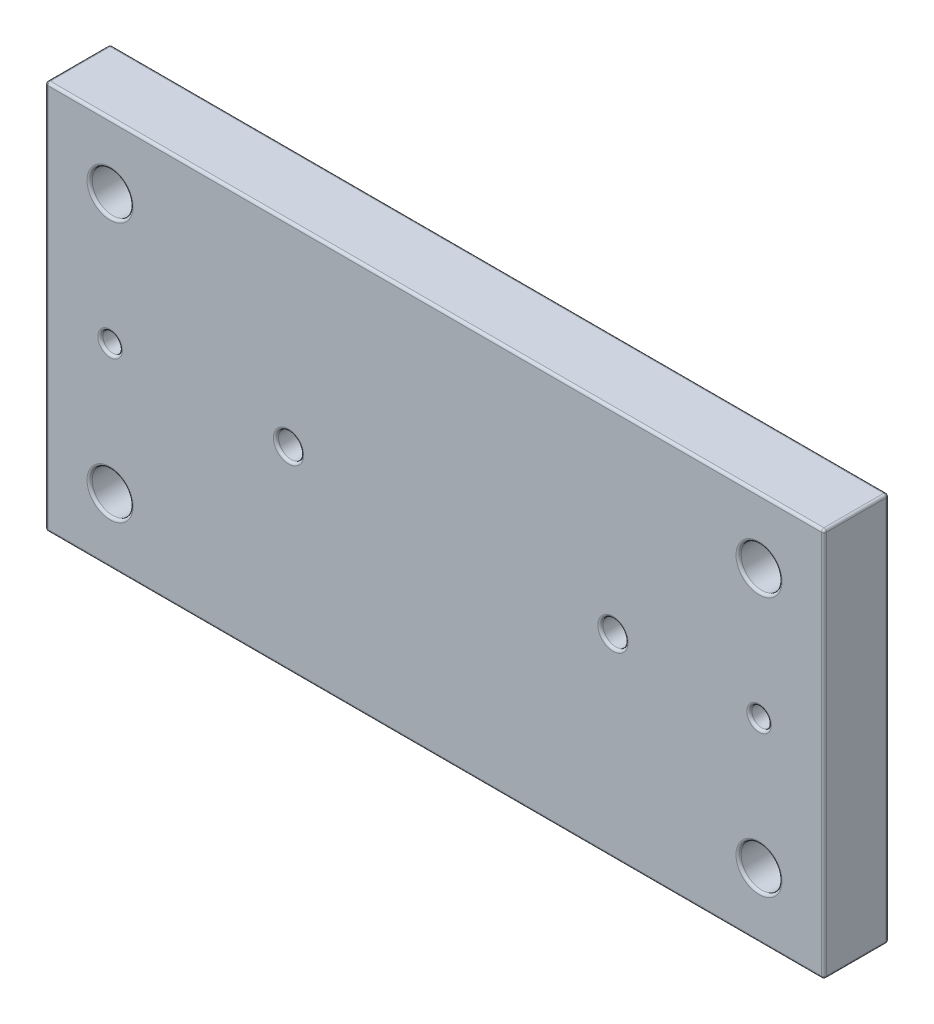
SolidWorks part; units mm, degrees
ref_plane "Front Plane" through (0, 0, 0) normal (0, 0, 1) x (1, 0, 0)
ref_plane "Top Plane" through (0, 0, 0) normal (0, 1, 0) x (1, 0, 0)
ref_plane "Right Plane" through (0, 0, 0) normal (1, 0, 0) x (0, 0, -1)
sketch "Sketch1" plane through (0, 0, 0) normal (0, 0, 1) x (1, 0, 0)
  line L1 (0, 0) -> (152.4, 0)
  line L2 (0, 0) -> (0, 76.2)
  line L3 (0, 76.2) -> (152.4, 76.2)
  line L4 (152.4, 0) -> (152.4, 76.2)
  dimension "D1" = 152.4
  dimension "D2" = 76.2
extrude "Extrude1" add sketch "Sketch1" along normal blind 12.7
hole_wizard "Ø8.0 (8) Diameter Hole1" positions "3DSketch1" profile "Sketch2" hole size "Ø8.0" standard "Ansi Metric" end condition up to next
sketch3d "3DSketch1"
  line L0 (152.4, 76.2, 12.7) -> (0, 76.2, 12.7) construction
  line L1 (0, 76.2, 12.7) -> (0, 0, 12.7) construction
  line L2 (152.4, 0, 12.7) -> (152.4, 76.2, 12.7) construction
  line L3 (0, 0, 12.7) -> (152.4, 0, 12.7) construction
  point P0 (139.7, 63.5, 12.7)
  point P2 (139.7, 12.7, 12.7)
  point P4 (12.7, 12.7, 12.7)
  point P6 (12.7, 63.5, 12.7)
  dimension "D1" = 12.7
  dimension "D2" = 12.7
  dimension "D3" = 12.7
  dimension "D4" = 12.7
  dimension "D5" = 12.7
  dimension "D6" = 12.7
  dimension "D7" = 12.7
  dimension "D8" = 12.7
sketch "Sketch2" plane through (139.7, 63.5, 12.7) normal (1, 0, 0) x (0, -1, 0)
  line L0 (0, 0) -> (0, 12.7)
  line L1 (0, 12.7) -> (4, 12.7)
  line L2 (4, 12.7) -> (4, 0)
  line L5 (4, 0) -> (0, 0)
  line L11 (0, -6.35) -> (0, 107.95) construction
  dimension "Thru Hole Dia." = 8
  dimension "Thru Hole Depth" = 12.7
hole_wizard "#10 (0.1935) Diameter Hole1" positions "3DSketch3" profile "Sketch4" hole size "#10" standard "Ansi Inch" end condition up to next
sketch3d "3DSketch3"
  line L0 (0, 0, 12.7) -> (152.4, 0, 12.7) construction
  line L1 (0, 76.2, 12.7) -> (0, 0, 12.7) construction
  point P0 (47.625, 38.1, 12.7)
  point P2 (111.125, 38.1, 12.7)
  dimension "D1" = 63.5
  dimension "D2" = 38.1
  dimension "D3" = 38.1
  dimension "D4" = 47.625
sketch "Sketch4" plane through (47.625, 38.1, 12.7) normal (1, 0, 0) x (0, -1, 0)
  line L0 (0, 0) -> (0, 12.7)
  line L1 (0, 12.7) -> (2.4574, 12.7)
  line L2 (2.4574, 12.7) -> (2.4574, 0)
  line L5 (2.4574, 0) -> (0, 0)
  line L11 (0, -6.35) -> (0, 107.95) construction
  dimension "Thru Hole Dia." = 4.9149
  dimension "Thru Hole Depth" = 12.7
hole_wizard "#10-24 Tapped Hole1" positions "3DSketch4" profile "Sketch5" tap size "#10-24" standard "Ansi Inch" end condition up to next
sketch3d "3DSketch4"
  line L4 (12.7, 63.5, 12.7) -> (12.7, 12.7, 12.7)
  line L5 (12.7, 63.5, 0) -> (12.7, 63.5, 12.7) construction
  line L6 (12.7, 12.7, 0) -> (12.7, 12.7, 12.7) construction
  line L8 (139.7, 63.5, 12.7) -> (139.7, 12.7, 12.7)
  line L9 (139.7, 63.5, 0) -> (139.7, 63.5, 12.7) construction
  line L10 (139.7, 12.7, 0) -> (139.7, 12.7, 12.7) construction
  point P0 (12.7, 38.1, 12.7)
  point P2 (139.7, 38.1, 12.7)
sketch "Sketch5" plane through (12.7, 38.1, 12.7) normal (1, 0, 0) x (0, -1, 0)
  line L0 (0, 0) -> (0, 12.7)
  line L1 (0, 12.7) -> (1.8986, 12.7)
  line L2 (1.8986, 12.7) -> (1.8986, 0)
  line L5 (1.8986, 0) -> (0, 0)
  line L11 (0, -6.35) -> (0, 107.95) construction
  dimension "Thread Major Dia." = 3.7973
  dimension "Thru Tap Drill Depth" = 12.7
fillet "Fillet1" radius 0.508 28 edges at (152.4, 0, 6.35) (152.4, 76.2, 6.35) (0, 76.2, 6.35) (0, 0, 6.35) (76.2, 0, 0) (152.4, 38.1, 0) (76.2, 76.2, 0) (0, 38.1, 0) (8.7, 63.5, 0) (8.7, 12.7, 0) (135.7, 12.7, 0) (135.7, 63.5, 0) (143.7, 63.5, 12.7) (143.7, 12.7, 12.7) (76.2, 76.2, 12.7) (152.4, 38.1, 12.7) (76.2, 0, 12.7) (0, 38.1, 12.7) (16.7, 63.5, 12.7) (16.7, 12.7, 12.7) (108.6676, 38.1, 0) (45.1676, 38.1, 0) (113.5824, 38.1, 12.7) (50.0824, 38.1, 12.7) (137.8014, 38.1, 0) (10.8014, 38.1, 0) (14.5986, 38.1, 12.7) (141.5986, 38.1, 12.7)
